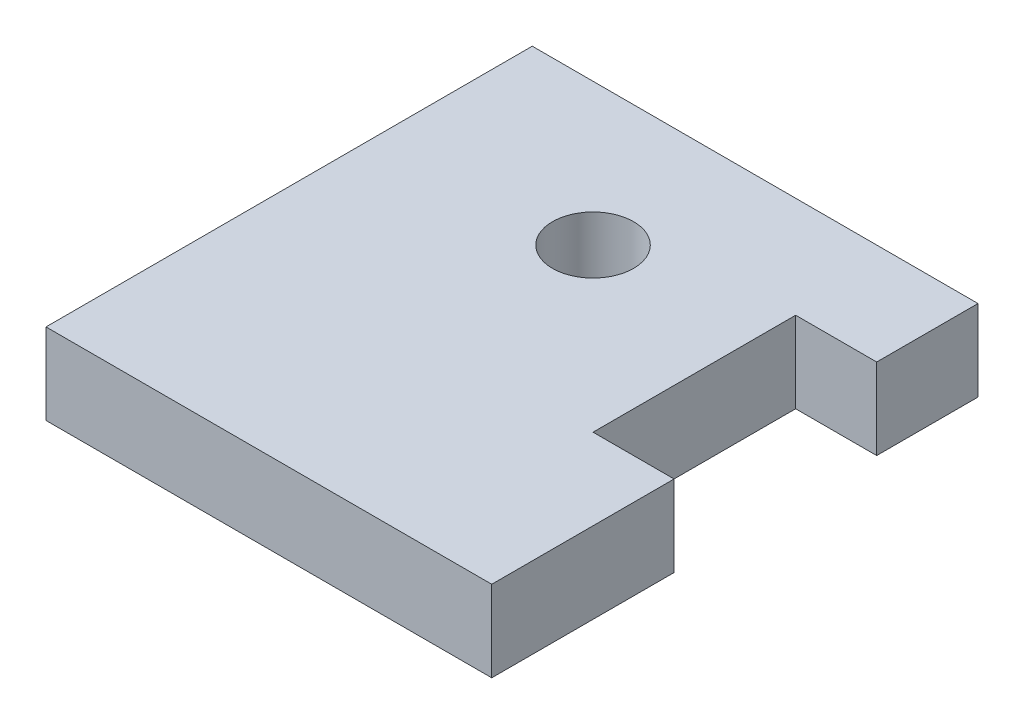
SolidWorks part; units mm, degrees
ref_plane "Front Plane" through (0, 0, 0) normal (0, 0, 1) x (1, 0, 0)
ref_plane "Top Plane" through (0, 0, 0) normal (0, 1, 0) x (1, 0, 0)
ref_plane "Right Plane" through (0, 0, 0) normal (1, 0, 0) x (0, 0, -1)
sketch "Sketch1" plane through (0, 0, 0) normal (0, 1, 0) x (1, 0, 0)
  line L9 (0, 0) -> (22, 0)
  line L17 (0, 0) -> (0, 24)
  line L18 (0, 24) -> (22, 24)
  line L19 (22, 0) -> (22, 9)
  line L20 (22, 19) -> (18, 19)
  line L22 (22, 9) -> (18, 9)
  line L23 (18, 19) -> (18, 9)
  line L24 (22, 19) -> (22, 24)
  circle A1 centre (10, 17) radius 2
  point P9 (0, 0)
  dimension "D6" = 7
  dimension "D7" = 4
  dimension "D1" = 24
  dimension "D2" = 22
  dimension "D3" = 4
  dimension "D4" = 5
  dimension "D5" = 10
  dimension "D8" = 10
extrude "Boss-Extrude1" add sketch "Sketch1" along normal blind 4
